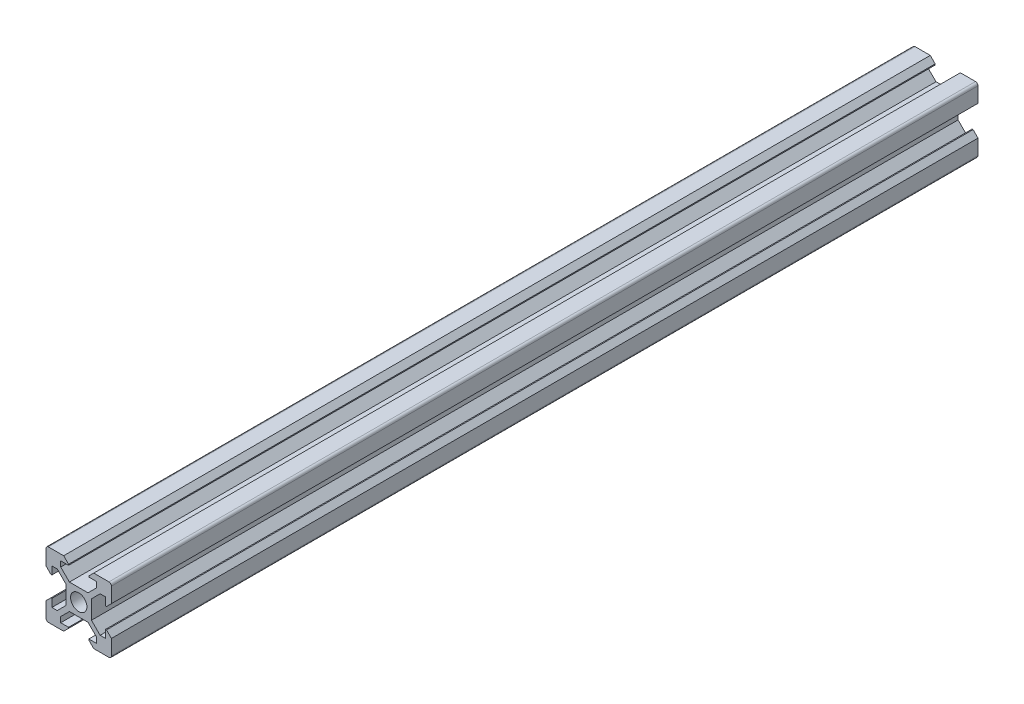
SolidWorks part; units mm, degrees
other "Markup1"
sketch "Sketch1" plane through (10, 10, 480) normal (0.5774, 0.5773, 0.5774) x (0.7071, 0, -0.7071)
ref_plane "Alzado" through (0, 0, 0) normal (0, 0, 1) x (1, 0, 0)
ref_plane "Planta" through (0, 0, 0) normal (0, 1, 0) x (1, 0, 0)
ref_plane "Vista lateral" through (0, 0, 0) normal (1, 0, 0) x (0, 0, -1)
sketch "Croquis1" plane through (0, 0, 0) normal (0, 0, 1) x (1, 0, 0)
  line L0 (-4.6, 10) -> (-3.1, 8.5)
  line L3 (-4.6, 10) -> (-9.25, 10)
  line L5 (-3.1, 8.5) -> (-3.1, 8.2)
  line L6 (-3.1, 8.2) -> (-5.5, 8.2)
  line L7 (-5.5, 8.2) -> (-5.5, 6.5607)
  line L8 (-5.5, 6.5607) -> (-2.84, 3.9007)
  line L9 (-2.84, 3.9007) -> (0, 3.9007)
  line L10 (0, 0) -> (-15.3499, 15.3499) construction
  line L11 (-3.9007, 2.84) -> (-3.9007, 0)
  line L12 (-6.5607, 5.5) -> (-3.9007, 2.84)
  line L13 (-8.2, 5.5) -> (-6.5607, 5.5)
  line L14 (-8.2, 3.1) -> (-8.2, 5.5)
  line L15 (-8.5, 3.1) -> (-8.2, 3.1)
  line L16 (-10, 4.6) -> (-10, 9.25)
  line L17 (-10, 4.6) -> (-8.5, 3.1)
  line L18 (10, 4.6) -> (8.5, 3.1)
  line L19 (10, 4.6) -> (10, 9.25)
  line L20 (8.5, 3.1) -> (8.2, 3.1)
  line L21 (8.2, 3.1) -> (8.2, 5.5)
  line L22 (8.2, 5.5) -> (6.5607, 5.5)
  line L23 (6.5607, 5.5) -> (3.9007, 2.84)
  line L24 (3.9007, 2.84) -> (3.9007, 0)
  line L25 (5.5, 6.5607) -> (2.84, 3.9007)
  line L26 (5.5, 8.2) -> (5.5, 6.5607)
  line L27 (3.1, 8.2) -> (5.5, 8.2)
  line L28 (3.1, 8.5) -> (3.1, 8.2)
  line L29 (4.6, 10) -> (9.25, 10)
  line L30 (4.6, 10) -> (3.1, 8.5)
  line L31 (2.84, 3.9007) -> (0, 3.9007)
  line L32 (4.6, -10) -> (3.1, -8.5)
  line L33 (4.6, -10) -> (9.25, -10)
  line L34 (3.1, -8.5) -> (3.1, -8.2)
  line L35 (3.1, -8.2) -> (5.5, -8.2)
  line L36 (5.5, -8.2) -> (5.5, -6.5607)
  line L37 (5.5, -6.5607) -> (2.84, -3.9007)
  line L38 (2.84, -3.9007) -> (0, -3.9007)
  line L39 (6.5607, -5.5) -> (3.9007, -2.84)
  line L40 (8.2, -5.5) -> (6.5607, -5.5)
  line L41 (8.2, -3.1) -> (8.2, -5.5)
  line L42 (8.5, -3.1) -> (8.2, -3.1)
  line L43 (10, -4.6) -> (10, -9.25)
  line L44 (10, -4.6) -> (8.5, -3.1)
  line L45 (3.9007, -2.84) -> (3.9007, 0)
  line L46 (-10, -4.6) -> (-8.5, -3.1)
  line L47 (-10, -4.6) -> (-10, -9.25)
  line L48 (-8.5, -3.1) -> (-8.2, -3.1)
  line L49 (-8.2, -3.1) -> (-8.2, -5.5)
  line L50 (-8.2, -5.5) -> (-6.5607, -5.5)
  line L51 (-6.5607, -5.5) -> (-3.9007, -2.84)
  line L52 (-3.9007, -2.84) -> (-3.9007, 0)
  line L53 (-5.5, -6.5607) -> (-2.84, -3.9007)
  line L54 (-5.5, -8.2) -> (-5.5, -6.5607)
  line L55 (-3.1, -8.2) -> (-5.5, -8.2)
  line L56 (-3.1, -8.5) -> (-3.1, -8.2)
  line L57 (-4.6, -10) -> (-9.25, -10)
  line L58 (-4.6, -10) -> (-3.1, -8.5)
  line L59 (-2.84, -3.9007) -> (0, -3.9007)
  circle A0 centre (0, 0) radius 2.5
  arc A1 (-9.25, 10) -> (-10, 9.25) centre (-9.25, 9.25) ccw
  arc A2 (10, 9.25) -> (9.25, 10) centre (9.25, 9.25) ccw
  arc A3 (9.25, -10) -> (10, -9.25) centre (9.25, -9.25) ccw
  arc A4 (-10, -9.25) -> (-9.25, -10) centre (-9.25, -9.25) ccw
  point P18 (-10, 10)
  point P37 (10, 10)
  point P55 (10, -10)
  point P73 (-10, -10)
  point P79 (0, 0)
  dimension "D1" = 5
  dimension "D5" = 0.75
  dimension "D2" = 10
  dimension "D3" = 10
  dimension "D4" = 4.6
  dimension "D6" = 5.5
  dimension "D7" = 135
  dimension "D8" = 0.75
  dimension "D9" = 225
  dimension "D10" = 2.84
  dimension "D11" = 1.8
  dimension "D12" = 3.1
  dimension "D13" = 4
extrude "Saliente-Extruir1" add sketch "Croquis1" along normal blind 265
